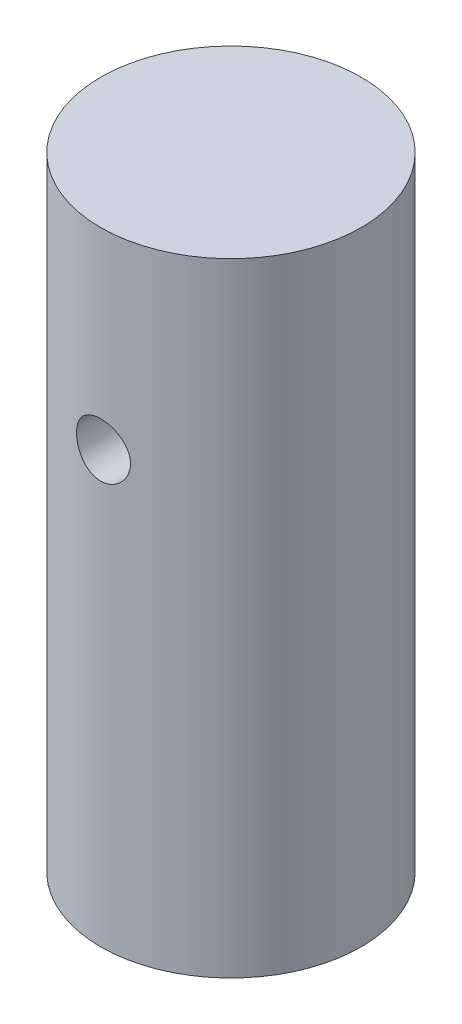
SolidWorks part; units mm, degrees
material "Gray Cast Iron"
ref_plane "Front Plane" through (0, 0, 0) normal (0, 0, 1) x (1, 0, 0)
ref_plane "Top Plane" through (0, 0, 0) normal (0, 1, 0) x (1, 0, 0)
ref_plane "Right Plane" through (0, 0, 0) normal (1, 0, 0) x (0, 0, -1)
sketch "Sketch1" plane through (0, 0, 0) normal (0, 1, 0) x (1, 0, 0)
  circle A0 centre (0, 0) radius 23
  dimension "D1" = 46
extrude "Boss-Extrude1" add sketch "Sketch1" along normal blind 110
sketch "Sketch2" plane through (0, 0, 0) normal (0, 0, 1) x (1, 0, 0)
  circle A0 centre (0, 76) radius 4.7625
  dimension "D2" = 9.525
  dimension "D1" = 76
extrude "Cut-Extrude1" cut sketch "Sketch2" against normal mid plane 50
ref_plane "Plane1" through (0, 76, 0) normal (0, 1, 0) x (1, 0, 0)
ref_axis "Axis1" through (0, 76, -25.3) along (0, 0, 1)
